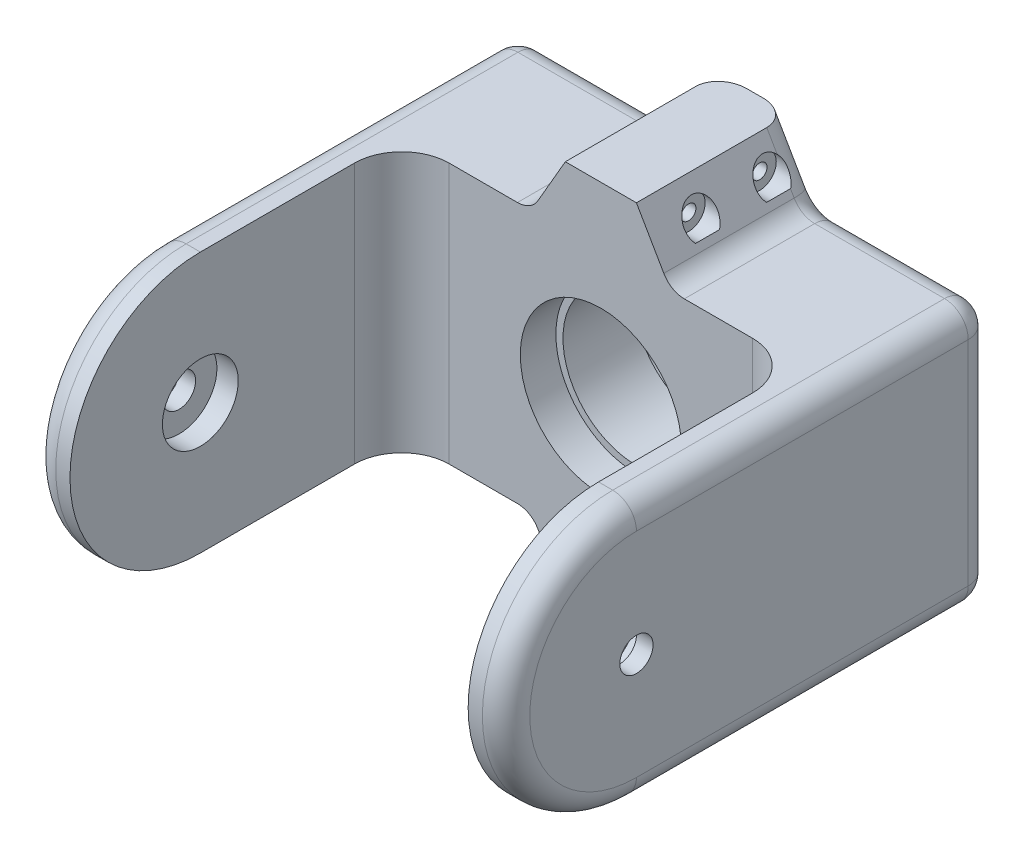
SolidWorks part; units mm, degrees
ref_plane "Front Plane" through (0, 0, 0) normal (0, 0, 1) x (1, 0, 0)
ref_plane "Top Plane" through (0, 0, 0) normal (0, 1, 0) x (1, 0, 0)
ref_plane "Right Plane" through (0, 0, 0) normal (1, 0, 0) x (0, 0, -1)
sketch "Sketch1" plane through (0, 0, 0) normal (0, 0, 1) x (1, 0, 0)
  circle A2 centre (0, 0) radius 34
  circle A3 centre (0, 0) radius 34 construction
  circle A4 centre (0, 0) radius 31
  circle A5 centre (0, 0) radius 30 construction
  dimension "D1" = 1
extrude "Centre Hole for L2" add sketch "Sketch1" along normal blind 30 contours A4 | A2
sketch "Sketch2" plane through (0, 0, 30) normal (0, 0, 1) x (1, 0, 0)
  line L0 (0, 48.4974) -> (0, 0) construction
  line L5 (-100, 55) -> (-100, -55)
  line L12 (0, 0) -> (72.986, 0) construction
  line L16 (-100, 55) -> (100, 55)
  line L17 (100, 55) -> (100, -55)
  line L18 (-100, -55) -> (100, -55)
  circle A0 centre (0, 0) radius 34
  circle A1 centre (0, 0) radius 34 construction
  circle A5 centre (0, 0) radius 34
  point P13 (0, 55)
  dimension "D1" = 100
  dimension "D2" = 110
extrude "Main Structure" add sketch "Sketch2" along normal blind 100 and the other way blind 50 separate body contours L5 L18 L17 L16 | A5
sketch "Sketch3" plane through (-100, 0, 0) normal (-1, 0, 0) x (0, 0, 1)
  line L0 (130, 55) -> (130, -55) construction
  line L1 (130, 55) -> (130, -55)
  line L2 (-20, 55) -> (130, 55) construction
  arc A0 (130, 55) -> (130, -55) centre (130, 0) cw
extrude "Bearing Curve" add sketch "Sketch3" against normal blind 16 contours A0 L1
mirror "Mirror7" about plane through (0, 0, 0) normal (1, 0, 0) of "Bearing Curve"
sketch "Sketch6" plane through (-100, 0, 0) normal (-1, 0, 0) x (0, 0, 1)
  circle A0 centre (130, 0) radius 7
  dimension "D1" = 14
extrude "Cut-Extrude2" cut sketch "Sketch6" against normal up to surface (16 mm away) up to face at (-84, 0, 157.5)
sketch "Sketch4" plane through (0, 55, 0) normal (0, 1, 0) x (1, 0, 0)
  line L0 (0, -110) -> (0, 20) construction
  line L1 (-84, -130) -> (84, -130) construction
  line L2 (-100, 20) -> (100, 20) construction
  line L3 (-84, -130) -> (-84, -65)
  line L4 (-64, -45) -> (64, -45)
  line L5 (-84, -130) -> (84, -130)
  line L6 (84, -130) -> (84, -65)
  arc A0 (-84, -65) -> (-64, -45) centre (-64, -65) cw
  arc A1 (84, -65) -> (64, -45) centre (64, -65) ccw
  point P17 (0, -130)
  point P20 (0, -45)
  dimension "D2" = 20
  dimension "D1" = 65
extrude "Wrist Cutout" cut sketch "Sketch4" against normal through all
sketch "Sketch9" plane through (-84, 0, 0) normal (1, 0, 0) x (0, 0, -1)
  circle A0 centre (-130, 0) radius 16
  dimension "D1" = 32
extrude "Cut-Extrude3" cut sketch "Sketch9" against normal blind 9
mirror "Mirror6" about plane through (0, 0, 0) normal (1, 0, 0) of "Cut-Extrude2", "Cut-Extrude3"
fillet "Fillet2" radius 10 2 edges at (-100, 0, -20) (100, 0, -20)
sketch "Sketch10" plane through (0, 0, -20) normal (0, 0, -1) x (-1, 0, 0)
  line L0 (0, 55) -> (0, 80) construction
  line L1 (90, 55) -> (-90, 55) construction
  line L2 (15, 80) -> (-15, 80)
  line L3 (-15, 80) -> (-29.4338, 55)
  line L4 (-29.4338, 55) -> (29.4338, 55)
  line L5 (15, 80) -> (29.4338, 55)
  dimension "D1" = 25
  dimension "D2" = 15
  dimension "D3" = 60
extrude "Boss-Extrude4" add sketch "Sketch10" against normal up to surface (65 mm away) up to face at (0, 0, 45)
sketch "Sketch11" plane through (0, 0, 0) normal (1, 0, 0) x (0, 0, -1)
  line L1 (-45, 67.5) -> (20, 67.5) construction
  line L2 (-45, 55) -> (-45, 80) construction
  line L3 (20, 80) -> (20, 55) construction
  circle A1 centre (5, 67.5) radius 3.1
  circle A2 centre (-25, 67.5) radius 3.1
  dimension "D1" = 6.2
  dimension "D2" = 15
  dimension "D3" = 30
extrude "Cut-Extrude6" cut sketch "Sketch11" against normal through all both and the other way through all
sketch "Sketch13" plane through (0, 0, 0) normal (1, 0, 0) x (0, 0, -1)
  circle A0 centre (5, 67.5) radius 7
  circle A1 centre (-25, 67.5) radius 7
  dimension "D1" = 14
extrude "Cut-Extrude8" cut sketch "Sketch13" against normal blind 8 from offset 25
mirror "Mirror8" about plane through (0, 0, 0) normal (0, 1, 0) of "Cut-Extrude6", "Cut-Extrude8", "Boss-Extrude4"
fillet "Fillet3" radius 10 4 edges at (-29.4338, -55, 12.5) (29.4338, -55, 12.5) (-29.4338, 55, 12.5) (29.4338, 55, 12.5)
fillet "Fillet1" radius 10 22 edges at (-100, 55, 60) (-100, -55, 60) (100, -55, 60) (100, 55, 60) (-100, 0, 185) (-20.7735, -70, -20) (-30.2073, -56.3397, -20) (-62.6036, -55, -20) (-97.0711, -55, -17.0711) (-20.7735, 70, -20) (-30.2073, 56.3397, -20) (-62.6036, 55, -20) (-97.0711, 55, -17.0711) (20.7735, 70, -20) (30.2073, 56.3397, -20) (62.6036, 55, -20) (97.0711, 55, -17.0711) (20.7735, -70, -20) (30.2073, -56.3397, -20) (62.6036, -55, -20) (97.0711, -55, -17.0711) (100, 0, 185)
